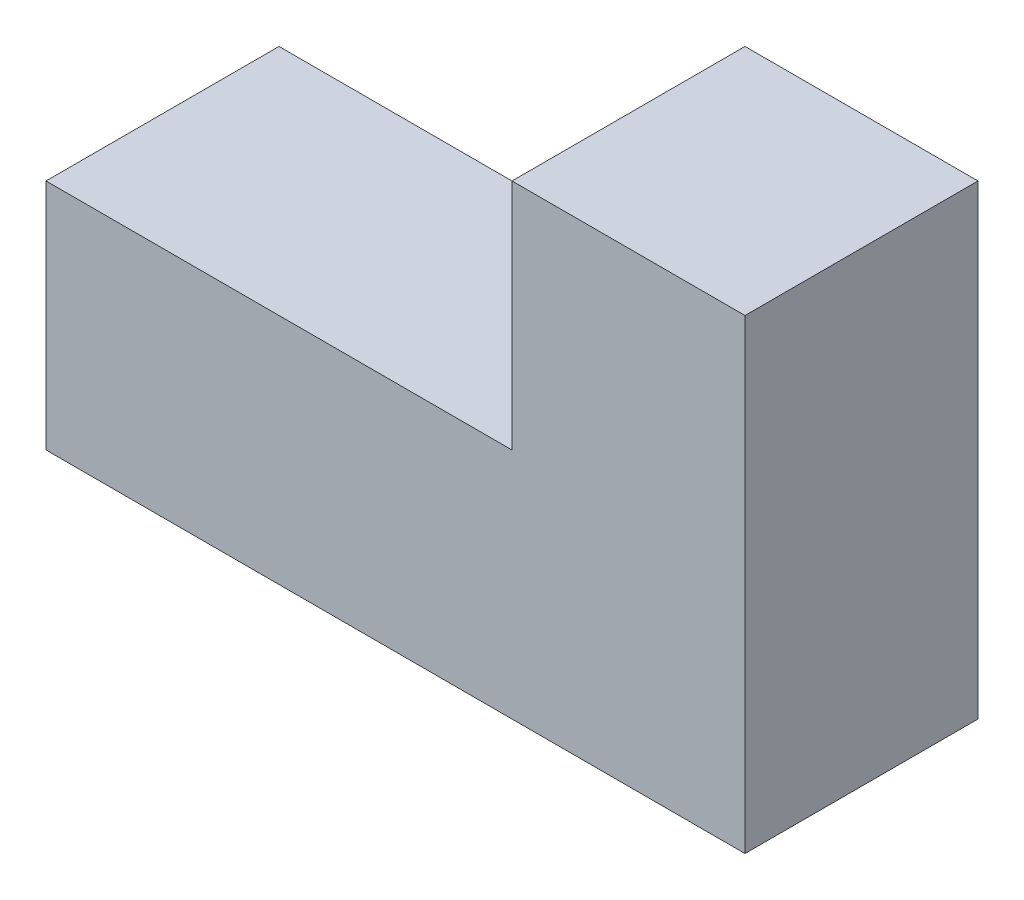
SolidWorks part; units mm, degrees
ref_plane "前基準面" through (0, 0, 0) normal (0, 0, 1) x (1, 0, 0)
ref_plane "上基準面" through (0, 0, 0) normal (0, 1, 0) x (1, 0, 0)
ref_plane "右基準面" through (0, 0, 0) normal (1, 0, 0) x (0, 0, -1)
ref_plane "平面1"
sketch "草圖1" plane through (0, 0, 0) normal (0, 0, 1) x (1, 0, 0)
  line L0 (0, 0) -> (90, 0)
  line L1 (90, 0) -> (90, 60)
  line L2 (90, 60) -> (60, 60)
  line L3 (60, 60) -> (60, 30)
  line L4 (60, 30) -> (0, 30)
  line L5 (0, 30) -> (0, 0)
  dimension "D1" = 90
  dimension "D2" = 60
  dimension "D3" = 30
  dimension "D4" = 30
  dimension "D5" = 60
extrude "擠出1" add sketch "草圖1" along normal blind 15 and the other way blind 15
